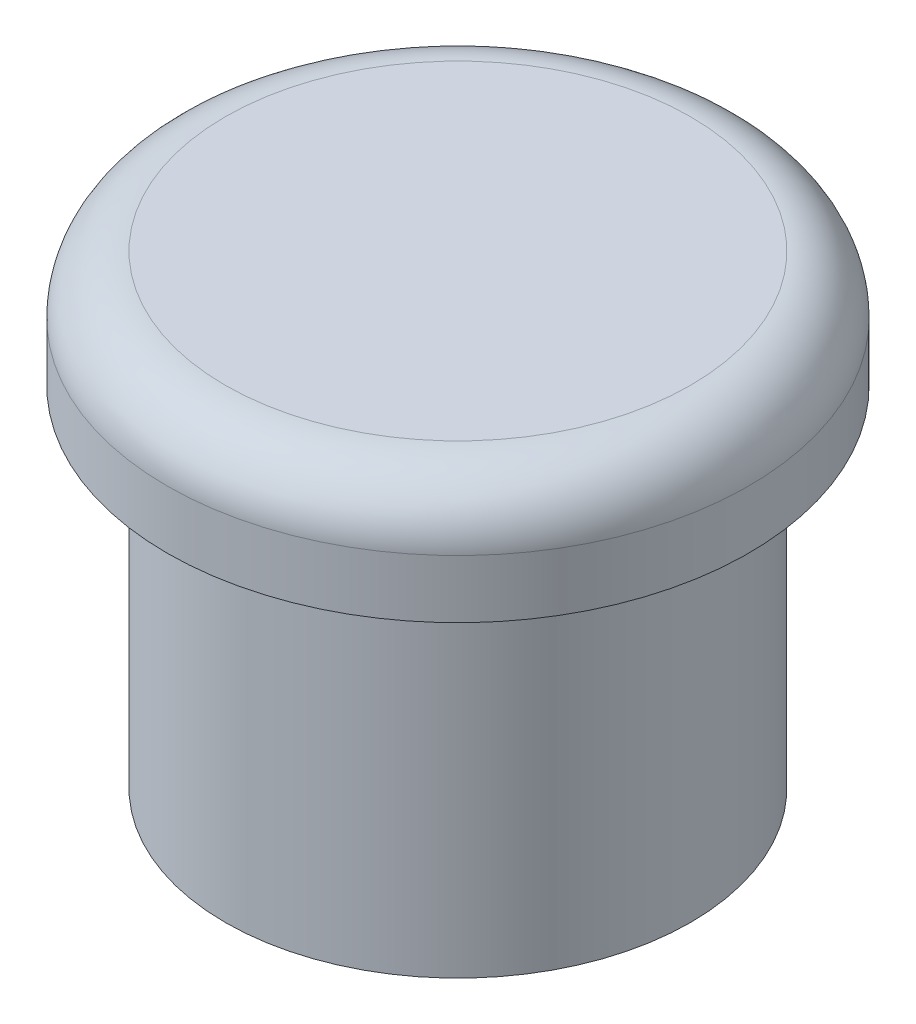
SolidWorks part; units mm, degrees
ref_plane "Front Plane" through (0, 0, 0) normal (0, 0, 1) x (1, 0, 0)
ref_plane "Top Plane" through (0, 0, 0) normal (0, 1, 0) x (1, 0, 0)
ref_plane "Right Plane" through (0, 0, 0) normal (1, 0, 0) x (0, 0, -1)
sketch "Sketch1" plane through (0, 0, 0) normal (0, 1, 0) x (1, 0, 0)
  circle A0 centre (0, 0) radius 1.5875
  circle A1 centre (0, 0) radius 2
  dimension "D1" = 3.175
  dimension "D2" = 4
extrude "Boss-Extrude1" add sketch "Sketch1" along normal blind 3
sketch "Sketch2" plane through (0, 3, 0) normal (0, 1, 0) x (1, 0, 0)
  circle A0 centre (0, 0) radius 2.5
  dimension "D1" = 5
extrude "Boss-Extrude2" add sketch "Sketch2" along normal blind 1
fillet "Fillet1" radius 0.5 1 edges at (0, 4, 2.5)
